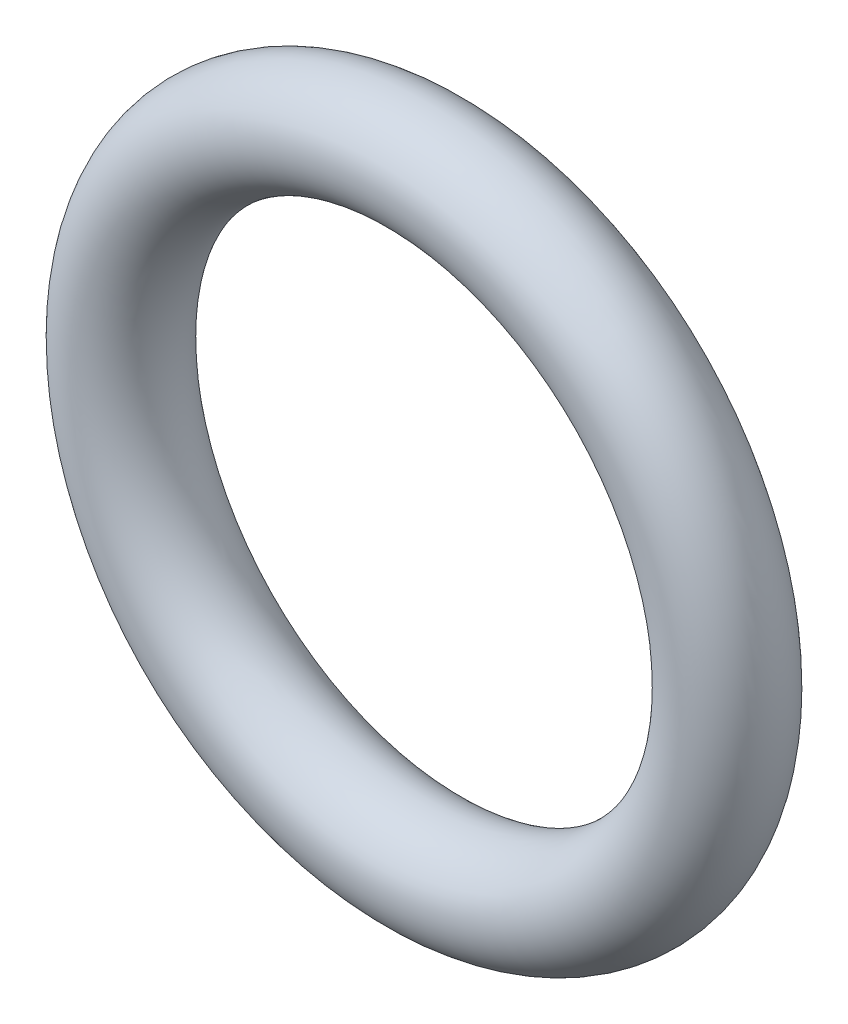
SolidWorks part; units mm, degrees
ref_plane "Front" through (0, 0, 0) normal (0, 0, 1) x (1, 0, 0)
ref_plane "Top" through (0, 0, 0) normal (0, 1, 0) x (1, 0, 0)
ref_plane "Right" through (0, 0, 0) normal (1, 0, 0) x (0, 0, -1)
sketch "Sketch1" plane through (0, 0, 0) normal (1, 0, 0) x (0, -1, 0)
  line L0 (0, -1.3081) -> (0, 1.3081) construction
  line L2 (-9.6812, 0) -> (9.6812, 0) construction
  line L3 (-6.1849, 0) -> (6.1849, 0) construction
  circle A0 centre (7.493, 0) radius 1.3081
  point P2 (0, 0)
  point P9 (6.1849, 0)
  point P10 (8.8011, 0)
  point P13 (7.493, 1.3081)
  point P14 (7.493, -1.3081)
  dimension "Width" = 2.6162
  dimension "ID" = 12.3698
revolve "Revolve1" add sketch "Sketch1" angle 360 about L0
ref_plane "Plane1" through (0, -7.493, 1.3081) normal (0, 0, 1) x (1, 0, 0)
sketch "Sketch2" plane through (0, -7.493, 1.3081) normal (0, 0, 1) x (1, 0, 0)
  circle A0 centre (0, 7.493) radius 7.493
  point P2 (0, 7.493)
